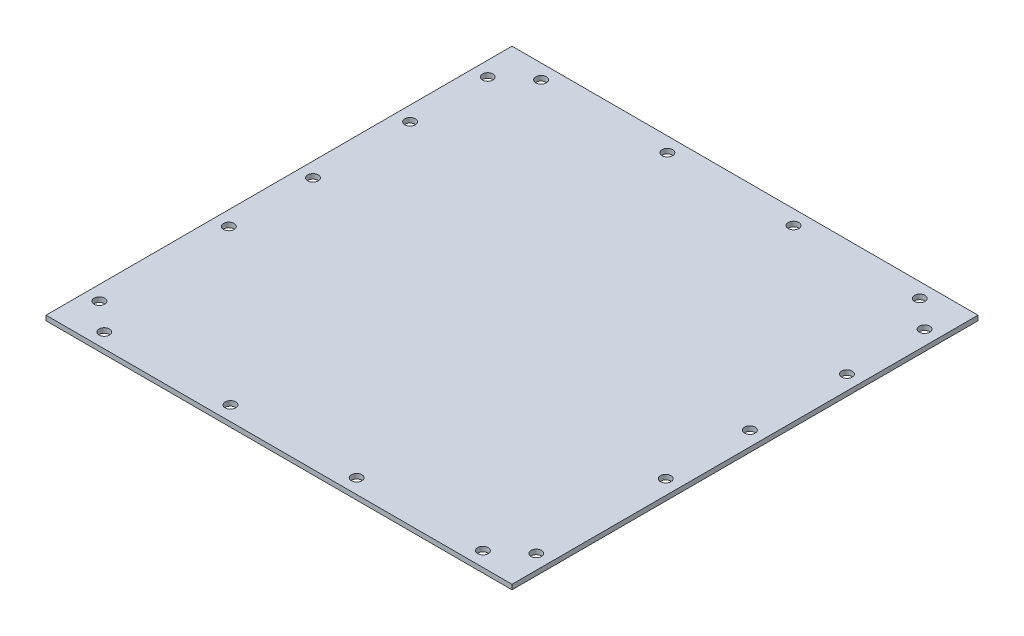
SolidWorks part; units mm, degrees
ref_plane "Front Plane" through (0, 0, 0) normal (0, 0, 1) x (1, 0, 0)
ref_plane "Top Plane" through (0, 0, 0) normal (0, 1, 0) x (1, 0, 0)
ref_plane "Right Plane" through (0, 0, 0) normal (1, 0, 0) x (0, 0, -1)
sketch "Sketch2" plane through (0, 0, 0) normal (0, 1, 0) x (1, 0, 0)
  line L0 (0, 0) -> (152.4, 0)
  line L1 (152.4, 0) -> (152.4, 152.4)
  line L2 (152.4, 152.4) -> (0, 152.4)
  line L3 (0, 152.4) -> (0, 0)
  dimension "D1" = 152.4
  dimension "D2" = 152.4
extrude "Boss-Extrude1" add sketch "Sketch2" along normal blind 1.5875
sketch "Sketch3" plane through (0, 1.5875, 0) normal (0, 1, 0) x (1, 0, 0)
  line L0 (0, 152.4) -> (4.7625, 152.4)
  line L1 (152.4, 152.4) -> (0, 152.4) construction
  line L2 (4.7625, 152.4) -> (4.7625, 0)
  line L3 (0, 0) -> (152.4, 0) construction
  line L4 (0, 152.4) -> (0, 147.6375)
  line L5 (0, 152.4) -> (0, 0) construction
  line L6 (0, 147.6375) -> (152.4, 147.6375)
  line L7 (152.4, 0) -> (152.4, 152.4) construction
  line L8 (152.4, 152.4) -> (147.6375, 152.4)
  line L9 (147.6375, 152.4) -> (147.6375, 0)
  line L10 (152.4, 0) -> (152.4, 4.7625)
  line L11 (152.4, 4.7625) -> (0, 4.7625)
  point P21 (4.7625, 139.7)
  point P23 (14.2875, 147.6375)
  point P24 (147.6375, 139.7)
  point P25 (138.1125, 4.7625)
  point P26 (4.7625, 12.7)
  dimension "D1" = 4.7625
  dimension "D2" = 4.7625
  dimension "D3" = 4.7625
  dimension "D4" = 4.7625
  dimension "D5" = 12.7
  dimension "D6" = 14.2875
  dimension "D7" = 12.7
  dimension "D8" = 14.2875
  dimension "D9" = 12.7
sketch "Sketch4" plane through (0, 1.5875, 0) normal (0, 1, 0) x (1, 0, 0)
  point P0 (14.2875, 147.6375)
  point P3 (147.6375, 139.7)
  point P6 (138.1125, 4.7625)
  point P9 (4.7625, 12.7)
sketch "Sketch6" plane through (0, 1.5875, 0) normal (0, 1, 0) x (1, 0, 0)
  line L0 (152.4, 4.7625) -> (0, 4.7625) construction
  line L1 (0, 152.4) -> (0, 0) construction
  point P0 (14.2875, 147.6375)
  point P3 (14.2875, 4.7625)
  dimension "D1" = 14.2875
hole_wizard "#5 Clearance Hole2" positions "Sketch6" profile "Sketch7" hole size "#5" standard "ANSI Inch" end condition through all
sketch "Sketch7" plane through (14.2875, 1.5875, -147.6375) normal (1, 0, 0) x (0, 0, 1)
  line L0 (0, 0) -> (0, 1.5875)
  line L1 (0, 1.5875) -> (1.7272, 1.5875)
  line L2 (1.7272, 1.5875) -> (1.7272, 0)
  line L5 (1.7272, 0) -> (0, 0)
  line L11 (0, -6.35) -> (0, 107.95) construction
  dimension "Thru Hole Dia." = 3.4544
  dimension "Thru Hole Depth" = 1.5875
sketch "Sketch8" plane through (0, 1.5875, 0) normal (0, 1, 0) x (1, 0, 0)
  point P0 (4.7625, 139.7)
  point P3 (147.6375, 139.7)
hole_wizard "#5 Clearance Hole3" positions "Sketch8" profile "Sketch9" hole size "#5" standard "ANSI Inch" end condition through all
sketch "Sketch9" plane through (4.7625, 1.5875, -139.7) normal (1, 0, 0) x (0, 0, 1)
  line L0 (0, 0) -> (0, 1.5875)
  line L1 (0, 1.5875) -> (1.7272, 1.5875)
  line L2 (1.7272, 1.5875) -> (1.7272, 0)
  line L5 (1.7272, 0) -> (0, 0)
  line L11 (0, -6.35) -> (0, 107.95) construction
  dimension "Thru Hole Dia." = 3.4544
  dimension "Thru Hole Depth" = 1.5875
pattern_linear "LPattern1" count 4 spacing 42.3333 along (0, 0, 1) skipping (1, 0) of "#5 Clearance Hole3"
pattern_linear "LPattern2" count 4 spacing 41.275 along (1, 0, 0) of "#5 Clearance Hole2"
sketch "Sketch10" plane through (0, 1.5875, 0) normal (0, 1, 0) x (1, 0, 0)
  line L0 (152.4, 0) -> (152.4, 152.4) construction
  line L1 (152.4, 152.4) -> (0, 152.4) construction
  line L2 (76.2, 152.4) -> (76.2, 0) construction
  line L3 (0, 0) -> (152.4, 0) construction
  point P0 (147.6375, 114.3)
  point P5 (147.6375, 82.55)
  point P10 (4.7625, 82.55)
  point P11 (4.7625, 114.3)
  dimension "D1" = 4.7625
  dimension "D2" = 38.1
  dimension "D3" = 31.75
hole_wizard "#5 Clearance Hole4" positions "Sketch10" profile "Sketch11" hole size "#5" standard "ANSI Inch"
sketch "Sketch11" plane through (147.6375, 1.5875, -114.3) normal (1, 0, 0) x (0, 0, 1)
  line L0 (0, 0) -> (0, 13.7378)
  line L1 (0, 13.7378) -> (1.7272, 12.7)
  line L2 (1.7272, 12.7) -> (1.7272, 0)
  line L5 (1.7272, 0) -> (0, 0)
  line L10 (0, 13.7378) -> (-1.7272, 12.7) construction
  line L11 (0, -6.35) -> (0, 107.95) construction
  dimension "Hole Dia." = 3.4544
  dimension "Hole Depth" = 12.7
  dimension "Drill Angle" = 118
